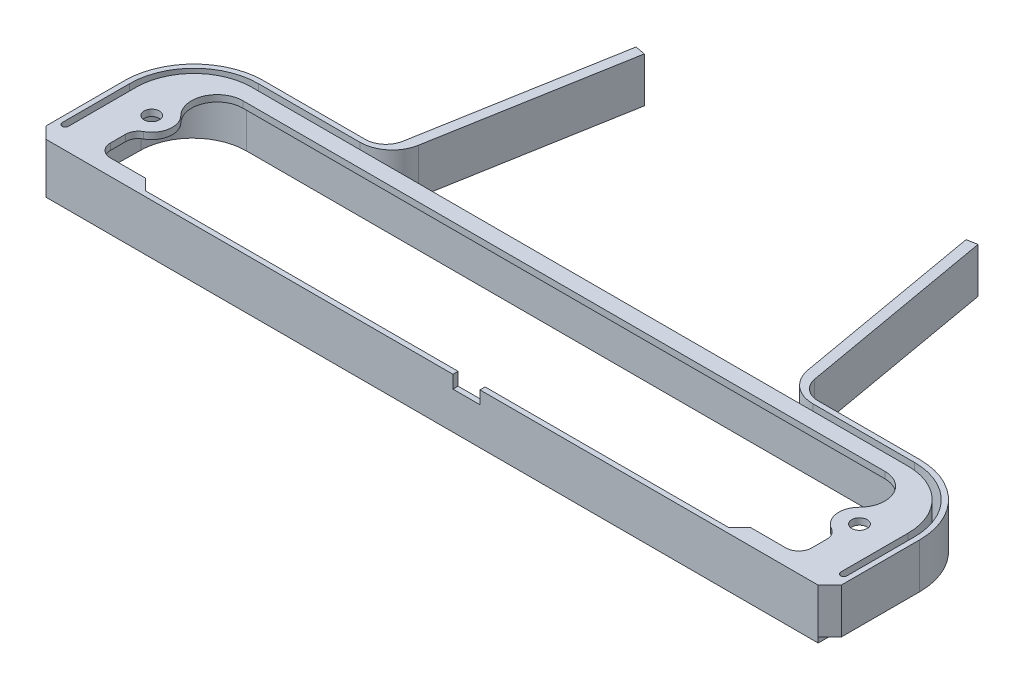
SolidWorks part; units mm, degrees
material "ABS"
ref_plane "Front" through (0, 0, 0) normal (0, 0, 1) x (1, 0, 0)
ref_plane "Top" through (0, 0, 0) normal (0, 1, 0) x (1, 0, 0)
ref_plane "Right" through (0, 0, 0) normal (1, 0, 0) x (0, 0, -1)
ref_axis "X" through (-80.9, 0, 0) along (1, 0, 0)
ref_axis "Y" through (0, -50, 0) along (0, 1, 0)
ref_axis "Z" through (0, 0, -80.9) along (0, 0, 1)
sketch "Sketch1" plane through (0, 0, 0) normal (0, 1, 0) x (1, 0, 0)
  line L0 (-60, 0) -> (-54.5, 0)
  line L2 (-49.8878, 20.5) -> (49.8878, 20.5)
  line L4 (54.5, 0) -> (60, 0)
  line L5 (60, 0) -> (60, 14)
  line L6 (51, 23) -> (-51, 23)
  line L7 (-60, 14) -> (-60, 0)
  line L8 (-54.5, 0) -> (54.5, 0)
  line L9 (-47, 0.8) -> (47, 0.8)
  line L10 (-54.5, 0) -> (-54.5, 0.8) construction
  line L11 (54.5, 0) -> (54.5, 0.8) construction
  line L12 (55, 11.43) -> (-55, 11.43) construction
  line L13 (0, 11.43) -> (0, 0) construction
  line L14 (54.5, 2.5) -> (47, 2.5)
  line L15 (47, 2.5) -> (47, 0.8)
  line L16 (-54.5, 2.5) -> (-47, 2.5)
  line L17 (-47, 2.5) -> (-47, 0.8)
  line L18 (-54.5, 0.8) -> (-54.5, 2.5) construction
  line L19 (-54.5, 0.8) -> (-47, 0.8) construction
  line L20 (54.5, 2.5) -> (54.5, 0.8) construction
  line L21 (47, 0.8) -> (54.5, 0.8) construction
  line L22 (54.5, 8.2693) -> (54.5, 2.5)
  line L23 (-54.5, 2.5) -> (-54.5, 8.2693)
  arc A0 (-52.7279, 13.6833) -> (-49.8878, 20.5) centre (-49.8878, 16.5) cw
  arc A1 (49.8878, 20.5) -> (52.7279, 13.6833) centre (49.8878, 16.5) cw
  arc A2 (60, 14) -> (51, 23) centre (51, 14) ccw
  arc A3 (-51, 23) -> (-60, 14) centre (-51, 14) ccw
  circle A4 centre (55, 11.43) radius 1.2
  circle A5 centre (-55, 11.43) radius 1.2
  arc A6 (52.7279, 13.6833) -> (54.5, 8.2693) centre (55, 11.43) ccw
  arc A7 (-52.7279, 13.6833) -> (-54.5, 8.2693) centre (-55, 11.43) cw
  dimension "D5" = 9
  dimension "D6" = 4
  dimension "D10" = 2.4
  dimension "D13" = 3.2
  dimension "D1" = 120
  dimension "D2" = 5.5
  dimension "D3" = 2.5
  dimension "D4" = 23
  dimension "D7" = 0.8
  dimension "D8" = 11.43
  dimension "D9" = 110
  dimension "D11" = 13
  dimension "D12" = 2.5
extrude "Boss-Extrude1" add sketch "Sketch1" along normal blind 1
sketch "Sketch8" plane through (0, 0, 0) normal (0, -1, 0) x (-1, 0, 0)
  line L0 (-59.2, 0.8) -> (59.2, 0.8)
  line L1 (59.2, 0.8) -> (59.2, 14)
  line L2 (51, 22.2) -> (-51, 22.2)
  line L3 (-59.2, 14) -> (-59.2, 0.8)
  line L4 (60, 0) -> (60, 14)
  line L5 (51, 23) -> (-51, 23)
  line L6 (-60, 14) -> (-60, 0)
  line L7 (-60, 0) -> (60, 0)
  line L8 (60, 0) -> (60, 14)
  line L9 (51, 23) -> (-51, 23)
  line L10 (-60, 14) -> (-60, 0)
  line L11 (-60, 0) -> (60, 0)
  arc A0 (59.2, 14) -> (51, 22.2) centre (51, 14) ccw
  arc A1 (-51, 22.2) -> (-59.2, 14) centre (-51, 14) ccw
  arc A2 (60, 14) -> (51, 23) centre (51, 14) ccw
  arc A3 (-51, 23) -> (-60, 14) centre (-51, 14) ccw
  arc A4 (60, 14) -> (51, 23) centre (51, 14) ccw
  arc A5 (-51, 23) -> (-60, 14) centre (-51, 14) ccw
  dimension "D1" = 0
  dimension "D2" = 0.8
extrude "Boss-Extrude2" add sketch "Sketch8" along normal blind 8.2 from surface starting at face at (55, 1, -10.23)
chamfer "Chamfer1" distance 1 angle 45 7 edges at (59.2, 0, -7.4) (56.7983, 0, -19.7983) (-59.2, 0, -7.4) (-56.7983, 0, -19.7983) (53.1, 0, -0.8) (-53.1, 0, -0.8) (0, 0, -22.2)
sketch "Sketch9" plane through (0, 0, 0) normal (1, 0, 0) x (0, 0, -1)
  line L0 (-2, -7.2) -> (23, -7.2)
  line L1 (23, -7.2) -> (-2, -6.7636)
  line L3 (-2, -6.7636) -> (-2, -7.2)
  dimension "D1" = 25
  dimension "D2" = 1
extrude "Cut-Extrude1" cut sketch "Sketch9" against normal through all both and the other way through all
sketch "Sketch11" plane through (0, 0, 0) normal (0, 0, 1) x (1, 0, 0)
  line L0 (3.25, 1) -> (3.25, -1)
  line L1 (-60, 1) -> (60, 1) construction
  line L2 (3.25, -1) -> (7.45, -1)
  line L3 (7.45, -1) -> (7.45, 1)
  line L4 (7.45, 1) -> (3.25, 1)
  line L5 (5.35, -1) -> (5.35, 1) construction
  line L7 (60, 1) -> (60, -6.7985) construction
  dimension "D1" = 54.65
  dimension "D2" = 4.2
  dimension "D3" = 2
extrude "Cut-Extrude2" cut sketch "Sketch11" against normal up to next
fillet "Fillet1" radius 2 4 edges at (-54.5, 0.5, -8.2693) (-54.5, 0.5, -2.5) (54.5, 0.5, -2.5) (54.5, 0.5, -8.2693)
chamfer "Chamfer2" distance 1.7 angle 45 2 edges at (-47, 0, -0.8) (47, 0, -0.8)
sketch "Sketch12" plane through (0, 0, 0) normal (0, 1, 0) x (1, 0, 0)
  line L0 (-35.1906, 24) -> (-35.1906, 24.8) construction
  line L1 (-60, 0) -> (60, 0) construction
  line L3 (-70.0161, 72.0463) -> (123.9526, 72.0463) construction
  line L9 (-60, 0) -> (-61.8, 1.8)
  line L10 (7.45, 0) -> (60, 0) construction
  line L11 (0, 38.0905) -> (0, 0) construction
  line L21 (-30.2666, 28.1318) -> (-25, 58)
  line L22 (-25, 58) -> (-26.5757, 58.2778)
  line L23 (-26.5757, 58.2778) -> (-32.0078, 27.4707)
  line L27 (51, 23) -> (-51, 23) construction
  line L31 (-60, 0) -> (-60, 3.5)
  line L32 (-60, 14) -> (-60, 0) construction
  line L34 (-61.8, 1.8) -> (-61.8, 14)
  line L35 (-51, 24.8) -> (-35.1906, 24.8)
  line L36 (-61, 3.5) -> (-61, 14)
  line L37 (-51, 24) -> (-35.1906, 24)
  line L39 (-51, 24) -> (-51, 24.8) construction
  line L40 (-61, 14) -> (-61.8, 14) construction
  arc A3 (-61.8, 14) -> (-51, 24.8) centre (-51, 14) cw
  arc A4 (-61, 14) -> (-51, 24) centre (-51, 14) cw
  arc A5 (-61, 3.5) -> (-60, 3.5) centre (-60.5, 3.5) ccw
  arc A7 (-51, 23) -> (-60, 14) centre (-51, 14) ccw construction
  arc A8 (-35.1906, 24) -> (-30.2666, 28.1318) centre (-35.1906, 29) ccw
  arc A9 (-35.1906, 24.8) -> (-32.0078, 27.4707) centre (-35.1906, 28.0319) ccw
  dimension "D7" = 5
  dimension "D3" = 72.0463
  dimension "D9" = 10
  dimension "D11" = 35
  dimension "D12" = 1.6
  dimension "D14" = 25
  dimension "D2" = 45
  dimension "D4" = 1
  dimension "D5" = 0.8
  dimension "D6" = 3.5
extrude "Boss-Extrude3" add sketch "Sketch12" against normal blind 7 from surface starting at face at (0.8231, 1, -7.7026)
mirror "Mirror2" about plane through (0, 0, 0) normal (1, 0, 0) of "Boss-Extrude3"
equation "\"D3@Sketch12\"=200-127.95373"
